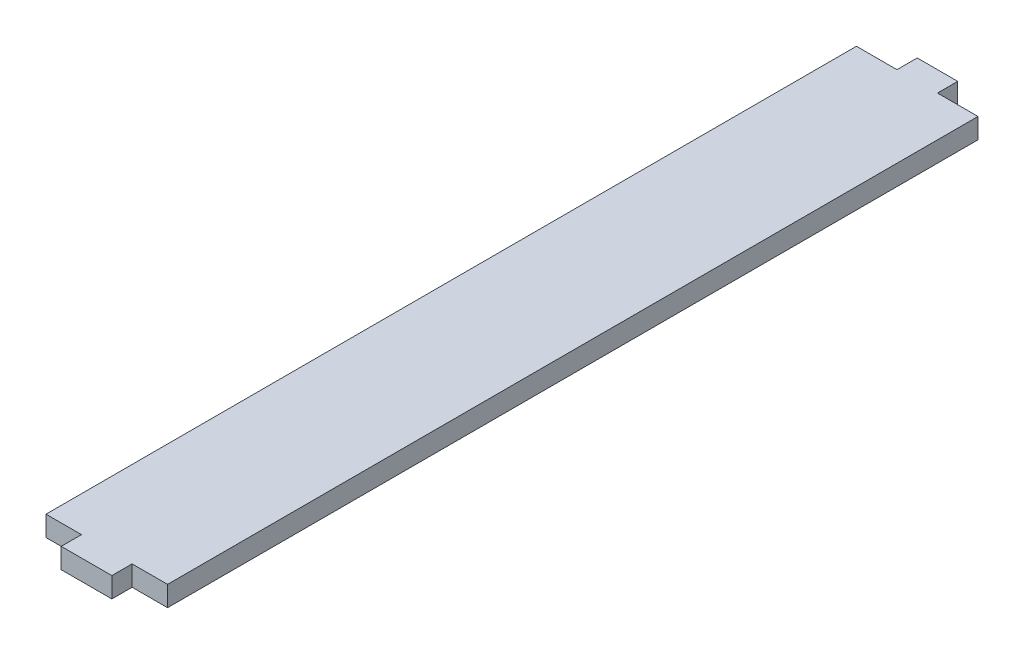
SolidWorks part; units mm, degrees
ref_plane "Front Plane" through (0, 0, 0) normal (0, 0, 1) x (1, 0, 0)
ref_plane "Top Plane" through (0, 0, 0) normal (0, 1, 0) x (1, 0, 0)
ref_plane "Right Plane" through (0, 0, 0) normal (1, 0, 0) x (0, 0, -1)
sketch "Sketch1" plane through (0, 0, 0) normal (0, 1, 0) x (1, 0, 0)
  line L0 (76.9168, -36.5625) -> (89.4168, -36.5625)
  line L1 (68.1668, 168.4375) -> (98.1668, 168.4375)
  line L2 (68.1668, 168.4375) -> (68.1668, -31.5625)
  line L3 (68.1668, -31.5625) -> (98.1668, -31.5625)
  line L4 (98.1668, 168.4375) -> (98.1668, -31.5625)
  line L5 (78.1668, 163.4375) -> (88.1668, 163.4375)
  line L6 (78.1668, 163.4375) -> (78.1668, 173.4375)
  line L7 (78.1668, 173.4375) -> (88.1668, 173.4375)
  line L8 (88.1668, 163.4375) -> (88.1668, 173.4375)
  line L9 (78.1668, 163.4375) -> (88.1668, 173.4375) construction
  line L10 (78.1668, 173.4375) -> (88.1668, 163.4375) construction
  line L11 (76.9168, -36.5625) -> (76.9168, -26.5625)
  line L12 (76.9168, -26.5625) -> (89.4168, -26.5625)
  line L13 (89.4168, -36.5625) -> (89.4168, -26.5625)
  line L14 (76.9168, -36.5625) -> (89.4168, -26.5625) construction
  line L15 (76.9168, -26.5625) -> (89.4168, -36.5625) construction
  point P4 (83.1668, 168.4375)
  point P9 (83.1668, -31.5625)
  dimension "D1" = 200
  dimension "D2" = 30
  dimension "D3" = 10
  dimension "D4" = 5
  dimension "D5" = 5
extrude "Boss-Extrude1" add sketch "Sketch1" along normal blind 5 contours L13 L3 L4 L1 L8 L5 L6 L2 L11 L12 | L0 L13 L12 L11 | L5 L8 L7 L6 region at (83.1668, 0, -68.6445)
equation "\"mat\"=\"mat@V1.assembly\""
equation "\"D4@Sketch1\"=\"mat\""
equation "\"D1@Boss-Extrude1\"=\"mat\""
equation "\"D5@Sketch1\" = \"mat\""
